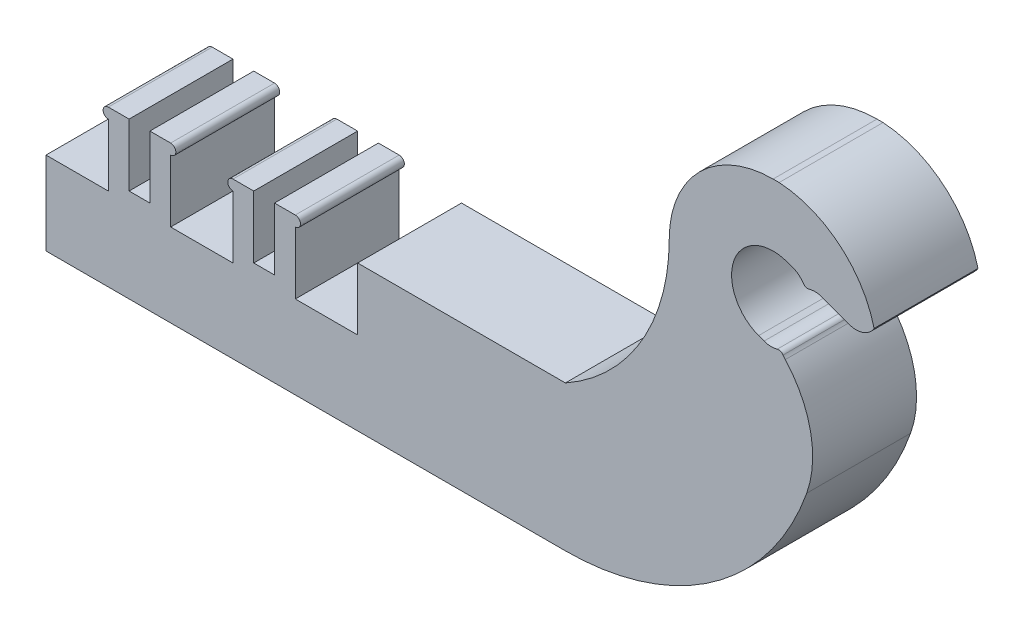
SolidWorks part; units mm, degrees
ref_plane "Front Plane" through (0, 0, 0) normal (0, 0, 1) x (1, 0, 0)
ref_plane "Top Plane" through (0, 0, 0) normal (0, 1, 0) x (1, 0, 0)
ref_plane "Right Plane" through (0, 0, 0) normal (1, 0, 0) x (0, 0, -1)
sketch "Sketch1" plane through (0, 0, 0) normal (0, 0, 1) x (1, 0, 0)
  line L0 (-20, -11.5) -> (-23, -11.5)
  line L1 (0, -999.6678) -> (0, 49000.3322) construction
  line L3 (-20, -11.5) -> (-20, -8.5)
  line L4 (-18.4916, -15.5) -> (-32, -15.5)
  line L5 (-32, -15.5) -> (-32, -11.5)
  line L6 (0.6983, 1.8741) -> (3.6509, 0.774)
  line L7 (-29, -8.5) -> (-29, -11.5)
  line L8 (-0.6983, -1.8741) -> (2.3217, -2.9994)
  line L9 (5, 1.7111) -> (5, 0.2907)
  line L10 (0.2907, 5) -> (0, 5)
  line L11 (-29, -11.5) -> (-26, -11.5)
  line L12 (-32, -11.5) -> (-32, -8.5)
  line L13 (-32, -8.5) -> (-29, -8.5)
  line L14 (-26, -8.5) -> (-23, -8.5)
  line L15 (-20, -8.5) -> (0, -8.5) construction
  line L16 (-23, -11.5) -> (-23, -8.5)
  line L17 (-23, -8.5) -> (-26, -8.5)
  line L18 (-26, -11.5) -> (-26, -8.5)
  line L19 (-29, -11.5) -> (-26, -11.5)
  line L20 (-26, -11.5) -> (-29, -11.5)
  line L21 (-23, -11.5) -> (-20, -11.5)
  line L22 (-18.4916, -15.5) -> (0, -15.5) construction
  line L23 (-20, -8.5) -> (-10, -8.5)
  line L24 (-18.4916, -15.5) -> (-10, -15.5)
  arc A0 (0, 5) -> (-5, 0) centre (0, 0) ccw
  arc A1 (0, 5) -> (0.595, 4.9645) centre (0, 0) cw
  arc A2 (0.2907, 5) -> (5, 0.2907) centre (0, 0) cw
  circle A3 centre (0, 0) radius 2
  arc A4 (5, 1.7111) -> (3.6509, 0.774) centre (4, 1.7111) cw
  arc A5 (-10, -8.5) -> (-5, 0) centre (-14.725, 0) ccw
  arc A6 (-10, -15.5) -> (2.3217, -2.9994) centre (-10, -3.177) ccw
  point P30 (5, -51.6467)
  dimension "D2" = 3
  dimension "D6" = 4
  dimension "D7" = 10
  dimension "D11" = 1
  dimension "D12" = 10
  dimension "D1" = 11.5
  dimension "D3" = 4
  dimension "D8" = 4
  dimension "D9" = 5
  dimension "D4" = 3
  dimension "D5" = 20
  dimension "D10" = 3
extrude "Boss-Extrude1" add sketch "Sketch1" along normal blind 5 contours L1 L8 A3 L6 L10 A0 L0 L16 L14 L18 L11 L7 L13 L12 L5 L4 | L1 L8 | L1 L6 L9 L10 region at (-11.5378, -8.9349, 0)
sketch "Sketch2" plane through (0, 0, 5) normal (0, 0, 1) x (1, 0, 0)
  line L0 (-0.6983, -1.8741) -> (2.3217, -2.9994) construction
  line L2 (1.4299, 1.6015) -> (1.8985, 1.427)
  line L3 (0.5019, -2.3213) -> (0.0334, -2.1467)
  line L6 (0.6983, 1.8741) -> (3.6509, 0.774) construction
  circle A0 centre (0, 0) radius 2 construction
  arc A1 (0.0334, -2.1467) -> (0.5019, -2.3213) centre (0.2676, -2.234) cw
  arc A2 (1.4299, 1.6015) -> (1.8985, 1.427) centre (1.6642, 1.5142) ccw
  arc A3 (0.6983, 1.8741) -> (-0.6983, -1.8741) centre (0, 0) ccw construction
  dimension "D1" = 0.25
extrude "Boss-Extrude2" add sketch "Sketch2" against normal blind 5
sketch "Sketch4" plane through (0, 0, 5) normal (0, 0, 1) x (1, 0, 0)
  line L0 (-29, -11.5) -> (-26, -11.5) construction
  line L1 (-32, -15.5) -> (-35, -15.5)
  line L2 (-32, -15.5) -> (-32, -11.5)
  line L3 (-32, -11.5) -> (-35, -11.5)
  line L4 (-35, -15.5) -> (-35, -11.5)
  line L5 (-29, -8.5) -> (-29, -11.5) construction
  line L6 (-32, -8.5) -> (-29, -8.5)
  line L7 (-32, -8.5) -> (-32, -8) construction
  line L8 (-32, -8) -> (-29, -8)
  line L9 (-29, -8.5) -> (-29, -8) construction
  line L10 (-26, -8.5) -> (-23, -8.5)
  line L11 (-26, -8.5) -> (-26, -8) construction
  line L12 (-26, -8) -> (-23, -8)
  line L13 (-23, -8.5) -> (-23, -8) construction
  arc A0 (-32, -8.5) -> (-32, -8) centre (-32, -8.25) cw
  arc A1 (-29, -8.5) -> (-29, -8) centre (-29, -8.25) ccw
  arc A2 (-26, -8) -> (-26, -8.5) centre (-26, -8.25) ccw
  arc A3 (-23, -8) -> (-23, -8.5) centre (-23, -8.25) cw
  dimension "D1" = 0.5
extrude "Boss-Extrude3" add sketch "Sketch4" against normal blind 5
sketch "Sketch5" plane through (0, 0, 5) normal (0, 0, 1) x (1, 0, 0)
  line L0 (-29, -8) -> (-32, -8) construction
  line L1 (-31, -8) -> (-30, -8)
  line L2 (-31, -8) -> (-31, -11)
  line L3 (-31, -11) -> (-30, -11)
  line L4 (-30, -8) -> (-30, -11)
  line L5 (-30.5, -11) -> (-30.5, -8) construction
  line L6 (-25, -8) -> (-24, -8)
  line L7 (-25, -8) -> (-25, -11)
  line L8 (-25, -11) -> (-24, -11)
  line L9 (-24, -8) -> (-24, -11)
  line L10 (-24.5, -11) -> (-24.5, -8) construction
  line L11 (-23, -8) -> (-26, -8) construction
  dimension "D1" = 3
  dimension "D2" = 1
extrude "Cut-Extrude4" cut sketch "Sketch5" against normal blind 5
fillet "Fillet1" radius 1 4 edges at (1.4299, 1.6015, 2.5) (1.8985, 1.427, 2.5) (0.5019, -2.3213, 2.5) (0.0334, -2.1467, 2.5)
fillet "Fillet2" radius 5 1 edges at (2.3217, -2.9994, 2.5)
